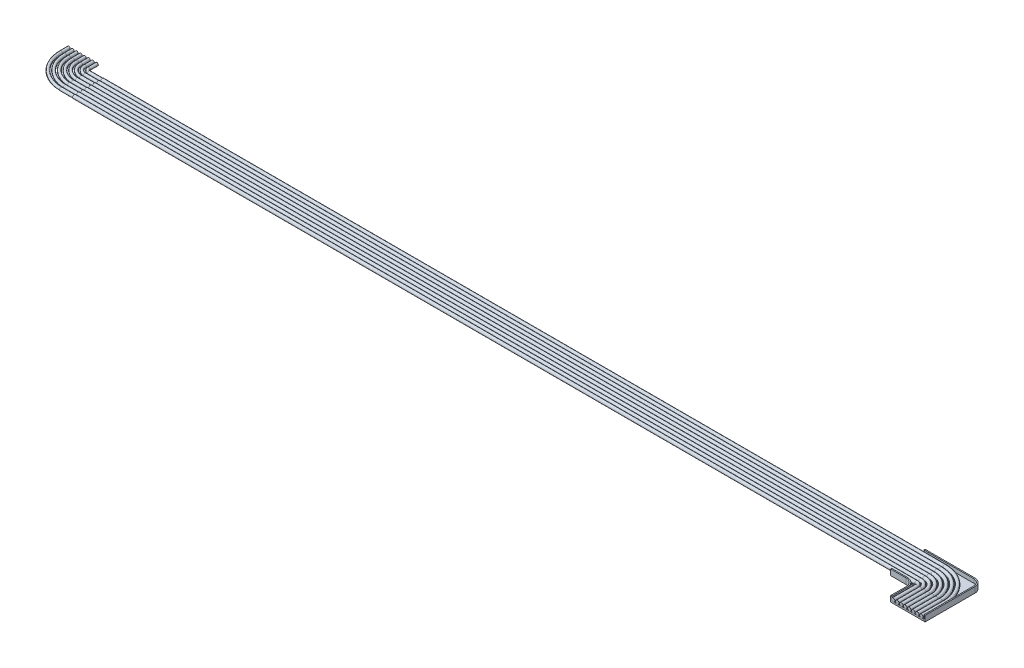
SolidWorks part; units mm, degrees
ref_plane "Alzado" through (0, 0, 0) normal (0, 0, 1) x (1, 0, 0)
ref_plane "Planta" through (0, 0, 0) normal (0, 1, 0) x (1, 0, 0)
ref_plane "Vista lateral" through (0, 0, 0) normal (1, 0, 0) x (0, 0, -1)
sketch "Croquis1" plane through (0, 0, 0) normal (0, 1, 0) x (1, 0, 0)
  line L0 (0, 0) -> (0, 270)
  line L1 (-130, 400) -> (-400, 400)
  line L2 (600, 0) -> (600, 870)
  line L3 (470, 1000) -> (-400, 1000)
  line L4 (600, 0) -> (600, 1000) construction
  line L5 (600, 1000) -> (-400, 1000) construction
  line L6 (0, 0) -> (0, 400) construction
  line L7 (0, 400) -> (-400, 400) construction
  line L8 (0, 0) -> (600, 0)
  line L9 (-400, 1000) -> (-400, 400)
  arc A0 (600, 870) -> (470, 1000) centre (470, 870) ccw
  arc A1 (0, 270) -> (-130, 400) centre (-130, 270) ccw
  point P13 (0, 400)
  dimension "D4" = 130
  dimension "D1" = 400
  dimension "D2" = 400
  dimension "D3" = 600
extrude "Saliente-Extruir1" add sketch "Croquis1" along normal blind 100
sketch "Croquis2" plane through (0, 100, 0) normal (0, 1, 0) x (1, 0, 0)
  line L0 (600, 0) -> (600, 870)
  line L1 (470, 1000) -> (-400, 1000)
  line L2 (580, 0) -> (580, 870)
  line L3 (-400, 400) -> (-130, 400)
  line L4 (0, 270) -> (0, 0)
  line L5 (470, 980) -> (-400, 980)
  line L6 (-400, 420) -> (-130, 420)
  line L7 (20, 270) -> (20, 0)
  line L8 (-400, 420) -> (-400, 980)
  line L9 (580, 0) -> (20, 0)
  arc A0 (600, 870) -> (470, 1000) centre (470, 870) ccw
  arc A1 (-130, 400) -> (0, 270) centre (-130, 270) cw
  arc A2 (580, 870) -> (470, 980) centre (470, 870) ccw
  arc A3 (-130, 420) -> (20, 270) centre (-130, 270) cw
  line M3 (0, 0) -> (600, 0)
  line M7 (-400, 1000) -> (-400, 400)
  dimension "D1" = 20
  dimension "D2" = 20
extrude "Cortar-Extruir1" cut sketch "Croquis2" against normal blind 70 contours L6 A3 L7 L2 A2 L5 M3 M7 region at (150.6483, 100, -550.6483)
sketch "Croquis3" plane through (0, 30, 0) normal (0, 1, 0) x (1, 0, 0)
  line L0 (-325.5404, 980) -> (-325.5404, 420)
  line L1 (470, 980) -> (-400, 980) construction
  line L2 (-400, 420) -> (-130, 420) construction
  line L3 (-325.5404, 420) -> (-265, 420)
  line L4 (-265, 420) -> (-265, 980)
  line L5 (-265, 980) -> (-325.5404, 980)
extrude "Cortar-Extruir2" cut sketch "Croquis3" against normal blind 70
pattern_linear "MatrizL1" count 3 spacing 130 along (1, 0, 0) of "Cortar-Extruir2"
sketch "Croquis4" plane through (0, 30, 0) normal (0, 1, 0) x (1, 0, 0)
  line L0 (580, 0) -> (20, 0)
  line L1 (20, 0) -> (20, 74)
  line L2 (20, 270) -> (20, 0) construction
  line L3 (20, 74) -> (580, 74)
  line L4 (580, 0) -> (580, 870) construction
  line L5 (580, 74) -> (580, 0)
  line L8 (20, 74) -> (20, 134)
  line L9 (20, 270) -> (20, 0) construction
  line L10 (20, 134) -> (580, 134)
  line L11 (580, 134) -> (580, 74)
  line M11 (20, 270) -> (20, 0)
  line M13 (580, 0) -> (580, 870)
  dimension "D1" = 74
  dimension "D2" = 60
extrude "Cortar-Extruir3" cut sketch "Croquis4" against normal blind 70 contours L10 L3 M11 M13 region at (300, 30, -104)
pattern_linear "MatrizL2" count 3 spacing 140 along (0, 0, -1) of "Cortar-Extruir3"
sketch "Croquis7" plane through (0, 30, 0) normal (0, 1, 0) x (1, 0, 0)
  circle A0 centre (-361.4354, 925.9571) radius 9.7289
extrude "Cortar-Extruir6" cut sketch "Croquis7" against normal blind 70
pattern_linear "MatrizL3" count 13 spacing 40 along (0, 0, 1) of "Cortar-Extruir6"
pattern_linear "MatrizL4" count 3 spacing 130 along (1, 0, 0) of "MatrizL3"
sketch "Croquis8" plane through (0, 30, 0) normal (0, 1, 0) x (1, 0, 0)
  circle A0 centre (532.7161, 37) radius 10.8653
extrude "Cortar-Extruir7" cut sketch "Croquis8" against normal blind 70
pattern_linear "MatrizL5" count 16 spacing 30 along (-1, 0, 0) of "Cortar-Extruir7"
pattern_linear "MatrizL6" count 4 spacing 140 along (0, 0, -1) of "MatrizL5"
sketch "Croquis9" plane through (0, 30, 0) normal (0, 1, 0) x (1, 0, 0)
  line L0 (580, 485.0168) -> (20, 485.0168)
  line L1 (580, 414) -> (580, 870) construction
  line L2 (20, 414) -> (20, 485.0168)
  line L3 (580, 485.0168) -> (580, 558.4626)
  line L4 (580, 558.4626) -> (20, 558.4626)
  line L5 (20, 558.4626) -> (20, 485.0168)
extrude "Cortar-Extruir8" cut sketch "Croquis9" against normal blind 70 contours L4 L5 L0 region at (300, 30, -521.7397)
sketch "Croquis10" plane through (-400, 0, 0) normal (-1, 0, 0) x (0, 0, 1)
  line L0 (-980, 30) -> (-980, 65) construction
  line L1 (-980, 30) -> (-980, 100) construction
  line L2 (-980, 65) -> (-420, 65) construction
  line L3 (-420, 30) -> (-420, 100) construction
  circle A0 centre (-943.9086, 65) radius 30
  circle A1 centre (-873.9086, 65) radius 30
  circle A2 centre (-803.9086, 65) radius 30
  circle A3 centre (-733.9086, 65) radius 30
  circle A4 centre (-663.9086, 65) radius 30
  circle A5 centre (-593.9086, 65) radius 30
  circle A6 centre (-523.9086, 65) radius 30
  circle A7 centre (-453.9086, 65) radius 30
  dimension "D1" = 60
  dimension "D2" = 8
sketch3d "Croquis3D1"
  line L0 (-400, 65, -943.9086) -> (-6.0982, 65, -943.9086)
  line L2 (543.9018, 65, -393.9086) -> (543.9018, 65, 9.3591)
  line L3 (580, 100, 0) -> (580, 100, -870) construction
  arc A0 (-6.0982, 65, -943.9086) -> (543.9018, 65, -393.9086) centre (-6.0982, 65, -393.9086) ccw
  point P6 (543.9018, 30, 0)
  point P7 (0, 0, 0)
  point P10 (543.9018, 65, -943.9086)
  point P11 (-6.0982, -485, -393.9086)
  dimension "D2" = 550
  dimension "D1" = 50.28
sweep "Barrer1" add profiles "Croquis10" path "Croquis3D1"
sketch "Croquis11" plane through (-400, 0, 0) normal (-1, 0, 0) x (0, 0, 1)
  circle A0 centre (-943.9086, 65) radius 30
  circle A1 centre (-873.9086, 65) radius 30
  circle A2 centre (-803.9086, 65) radius 30
  circle A3 centre (-733.9086, 65) radius 30
  circle A4 centre (-663.9086, 65) radius 30
  circle A5 centre (-593.9086, 65) radius 30
  circle A6 centre (-523.9086, 65) radius 30
  circle A7 centre (-453.9086, 65) radius 30
  dimension "D1" = 8
extrude "Saliente-Extruir2" add sketch "Croquis11" along normal blind 14300
sketch "Croquis12" plane through (-14700, 0, 0) normal (-1, 0, 0) x (0, 0, 1)
  circle A0 centre (-453.9086, 65) radius 25
  circle A1 centre (-523.9086, 65) radius 25
  circle A2 centre (-593.9086, 65) radius 25
  circle A3 centre (-663.9086, 65) radius 25
  circle A4 centre (-733.9086, 65) radius 25
  circle A5 centre (-803.9086, 65) radius 25
  circle A6 centre (-873.9086, 65) radius 25
  circle A7 centre (-943.9086, 65) radius 25
  dimension "D2" = 50
  dimension "D1" = 8
sketch3d "Croquis3D3"
  line L0 (-14700, 65, -453.9086) -> (-14932.38, 65, -453.9086)
  line L1 (-15482.38, 65, -1003.9086) -> (-15482.38, 65, -1139.9848)
  arc A0 (-14932.38, 65, -453.9086) -> (-15482.38, 65, -1003.9086) centre (-14932.38, 65, -1003.9086) ccw
  point P6 (-15482.38, 65, -453.9086)
  point P7 (-14932.38, -485, -1003.9086)
  point P8 (-15451.38, 65, -1139.9848)
  dimension "D2" = 550
  dimension "D1" = 782.38
sweep "Barrer2" add profiles "Croquis12" path "Croquis3D3"
sketch "Croquis14" plane through (-14700, 0, 0) normal (-1, 0, 0) x (0, 0, 1)
  circle A0 centre (-451.7446, 66.3195) radius 26.3069
  circle A1 centre (-521.7446, 66.3195) radius 26.3069
  circle A2 centre (-591.7446, 66.3195) radius 26.3069
  circle A3 centre (-661.7446, 66.3195) radius 26.3069
  circle A4 centre (-731.7446, 66.3195) radius 26.3069
  circle A5 centre (-801.7446, 66.3195) radius 26.3069
  circle A6 centre (-871.7446, 66.3195) radius 26.3069
  circle A7 centre (-941.7446, 66.3195) radius 26.3069
  dimension "D1" = 8
extrude "Saliente-Extruir3" add sketch "Croquis14" along normal blind 232
